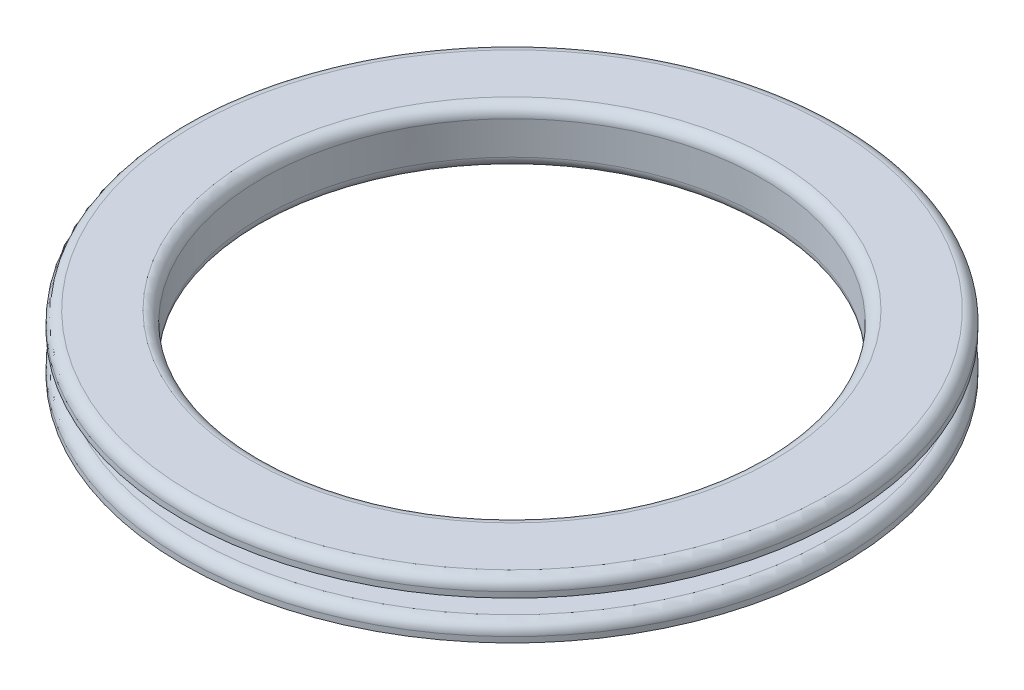
SolidWorks part; units mm, degrees
ref_plane "Front Plane" through (0, 0, 0) normal (0, 0, 1) x (1, 0, 0)
ref_plane "Top Plane" through (0, 0, 0) normal (0, 1, 0) x (1, 0, 0)
ref_plane "Right Plane" through (0, 0, 0) normal (1, 0, 0) x (0, 0, -1)
sketch "Sketch1" plane through (0, 0, 0) normal (0, 0, 1) x (1, 0, 0)
  line L0 (-9, 0) -> (-9, 2)
  line L1 (-9, 2) -> (-11.8718, 2)
  line L2 (-11.8718, 2) -> (-11.8718, 1.4)
  line L3 (-11.8718, 1.4) -> (-10.1534, 1.4)
  line L4 (-10.1534, 1.4) -> (-10.1534, 0.6)
  line L5 (-10.1534, 0.6) -> (-11.8718, 0.6)
  line L6 (-11.8718, 0.6) -> (-11.8718, 0)
  line L7 (-11.8718, 0) -> (-9, 0)
  line L8 (0, 7.2469) -> (0, -5.278) construction
  dimension "D1" = 9
  dimension "D2" = 2
  dimension "D3" = 0.6
  dimension "D4" = 0.6
  dimension "D5" = 0.8
revolve "Revolve1" add sketch "Sketch1" angle 360 about L8
fillet "Fillet1" radius 0.4 6 edges at (0, 2, 11.8718) (0, 0, 9) (0, 2, 9) (0, 0.6, 10.1534) (0, 1.4, 10.1534) (0, 0.6, 11.8718)
